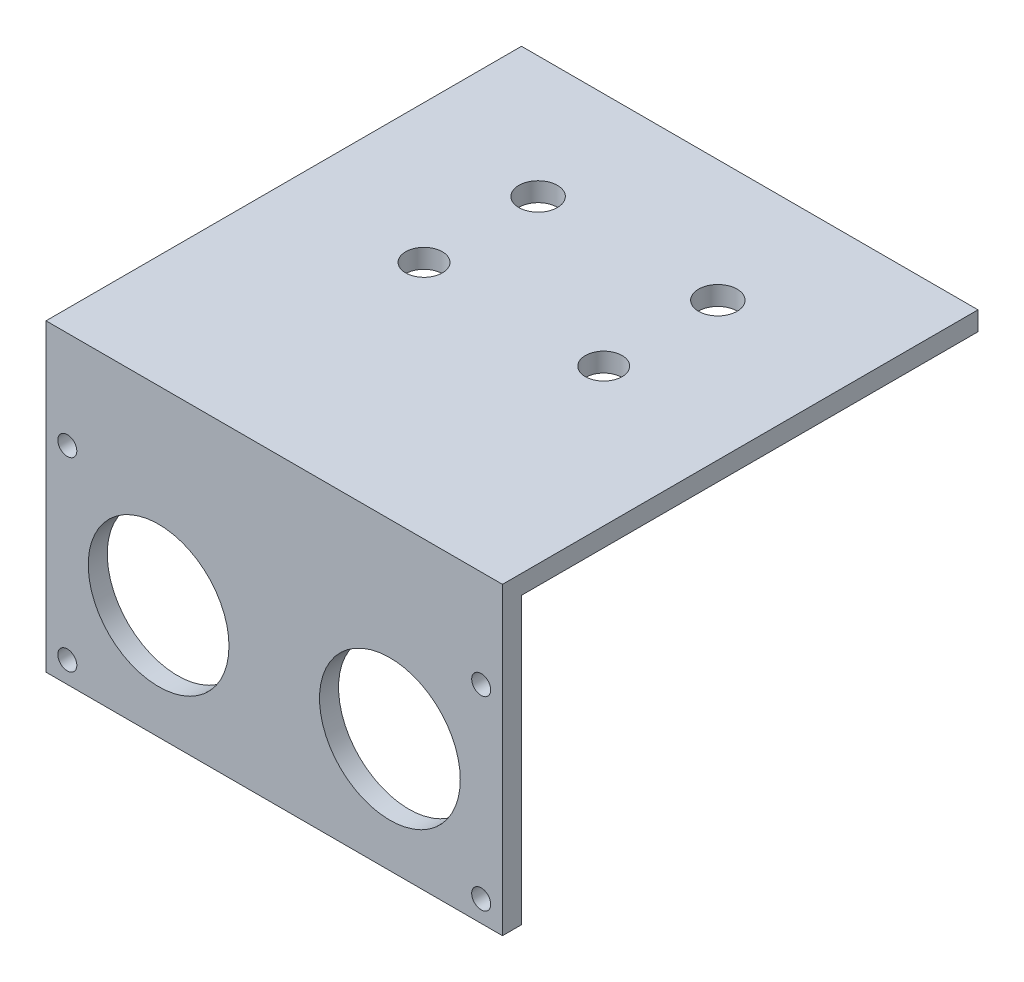
SolidWorks part; units mm, degrees
ref_plane "前视基准面" through (0, 0, 0) normal (0, 0, 1) x (1, 0, 0)
ref_plane "上视基准面" through (0, 0, 0) normal (0, 1, 0) x (1, 0, 0)
ref_plane "右视基准面" through (0, 0, 0) normal (1, 0, 0) x (0, 0, -1)
sketch "Sketch1" plane through (0, 0, 0) normal (0, 0, 1) x (1, 0, 0)
  line L0 (-76.2, 0) -> (-1.016, 0) construction
  line L1 (76.2, -38.1) -> (-76.2, -38.1)
  line L2 (76.2, -38.1) -> (76.2, 38.1)
  line L3 (76.2, 38.1) -> (-76.2, 38.1)
  line L4 (-76.2, -38.1) -> (-76.2, 38.1)
  line L5 (76.2, -38.1) -> (-76.2, 38.1) construction
  line L6 (76.2, 38.1) -> (-76.2, -38.1) construction
  line L8 (-76.2, 38.1) -> (76.2, 38.1)
  line L9 (-76.2, 38.1) -> (-76.2, 63.5)
  line L10 (-76.2, 63.5) -> (76.2, 63.5)
  line L11 (76.2, 38.1) -> (76.2, 63.5)
  circle A0 centre (-69.088, 30.988) radius 3.175
  circle A1 centre (69.088, 30.988) radius 3.175
  circle A2 centre (69.088, -30.988) radius 3.175
  circle A3 centre (-69.088, -30.988) radius 3.175
  circle A4 centre (-38.608, 0) radius 23.495
  circle A5 centre (38.608, 0) radius 23.495
  point P0 (0, 0)
  dimension "D7" = 6.35
  dimension "D8" = 6.35
  dimension "D11" = 46.99
  dimension "D12" = 46.99
  dimension "D1" = 76.2
  dimension "D2" = 152.4
  dimension "D3" = 30.988
  dimension "D4" = 30.988
  dimension "D5" = 69.088
  dimension "D6" = 69.088
  dimension "D9" = 38.608
  dimension "D10" = 38.608
  dimension "D13" = 25.4
extrude "Boss-Extrude2" add sketch "Sketch1" along normal blind 6.35 contours L3 L11 L10 L9 | L4 L1 L2 L3 A5 A4 A2 A1 A0 A3 region at (0, 0, 0) region at (0, 50.8, 0)
sketch "Sketch2" plane through (0, 0, 0) normal (0, 0, -1) x (-1, 0, 0)
  line L0 (76.2, -38.1) -> (76.2, 63.5) construction
  line L1 (-76.2, 63.5) -> (76.2, 63.5)
  line L2 (-76.2, 63.5) -> (-76.2, 57.15)
  line L3 (-76.2, 57.15) -> (76.2, 57.15)
  line L4 (76.2, 63.5) -> (76.2, 57.15)
  dimension "D1" = 6.35
extrude "Boss-Extrude3" add sketch "Sketch2" along normal blind 152.4
sketch "Sketch3" plane through (0, 63.5, 0) normal (0, 1, 0) x (1, 0, 0)
  line L0 (0, 152.4) -> (0, -6.35) construction
  line L1 (-76.2, 152.4) -> (76.2, 152.4) construction
  line L2 (-76.2, -6.35) -> (76.2, -6.35) construction
  circle A0 centre (-30, 73.65) radius 6.1298
  circle A1 centre (-30, 111.75) radius 6.4331
  circle A2 centre (30, 73.65) radius 6.1298
  circle A3 centre (30, 111.75) radius 6.4331
  dimension "D1" = 80
  dimension "D2" = 38.1
  dimension "D3" = 30
  dimension "D4" = 30
extrude "Cut-Extrude1" cut sketch "Sketch3" against normal blind 152.4
